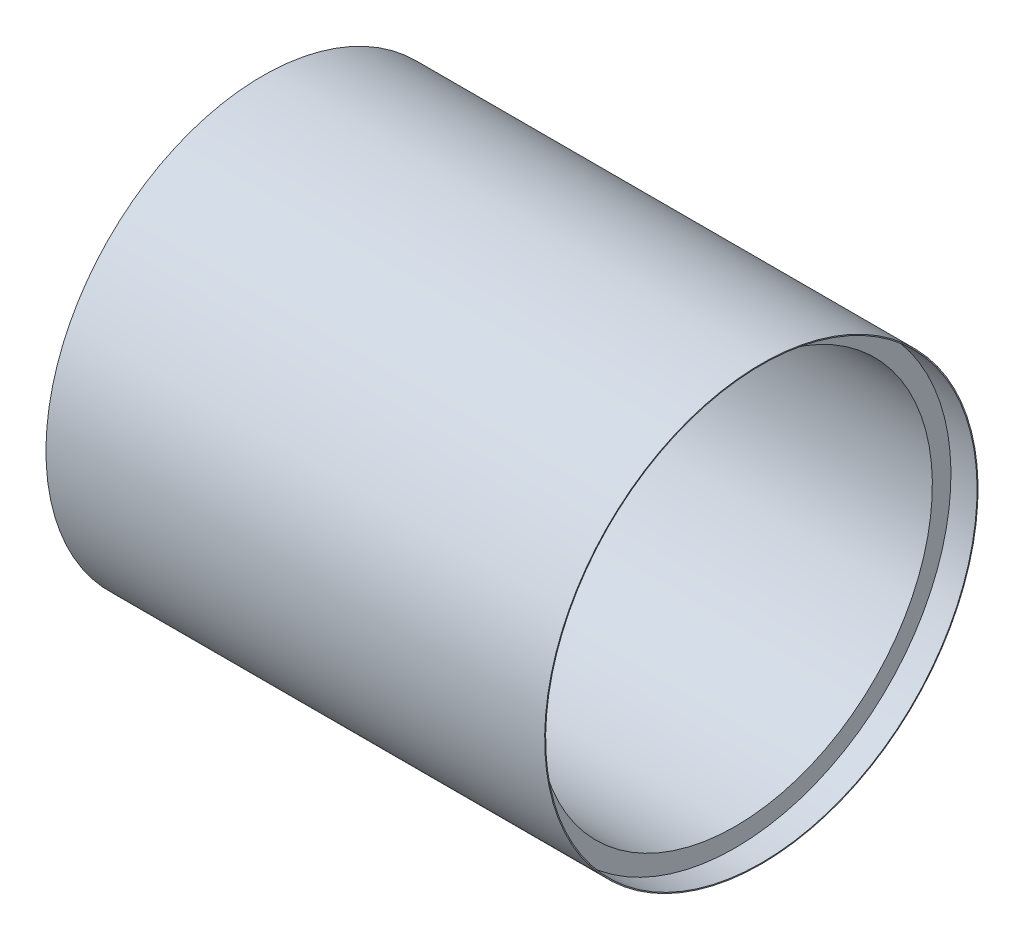
SolidWorks part; units mm, degrees
material "Carbon sandwich"
ref_plane "Front" through (0, 0, 0) normal (0, 0, 1) x (1, 0, 0)
ref_plane "Top" through (0, 0, 0) normal (0, 1, 0) x (1, 0, 0)
ref_plane "Right" through (0, 0, 0) normal (1, 0, 0) x (0, 0, -1)
sketch "Sketch1" plane through (0, 0, 0) normal (0, 0, 1) x (1, 0, 0)
  line L0 (39.1463, 83.9724) -> (49.3063, 83.9724)
  line L1 (49.3063, 83.9724) -> (49.3063, 76.7334)
  line L2 (49.3063, 76.7334) -> (223.1185, 76.7334)
  line L3 (223.1185, 76.7334) -> (223.1185, 83.9724)
  line L4 (223.1185, 83.9724) -> (233.2785, 83.9724)
  line L5 (233.2785, 83.9724) -> (233.2785, 84.3534)
  line L6 (233.2785, 84.3534) -> (39.1463, 84.3534)
  line L7 (39.1463, 84.3534) -> (39.1463, 83.9724)
  line L8 (0, 0) -> (134.0356, 0) construction
  dimension "D1" = 76.7334
  dimension "D2" = 0.381
  dimension "D3" = 10.16
  dimension "D4" = 10.16
  dimension "D5" = 173.8122
  dimension "D6" = 84.3534
  dimension "D7" = 0.381
revolve "Revolve1" add sketch "Sketch1" angle 360 about L8 region at (136.2124, 80.5644, 0)
